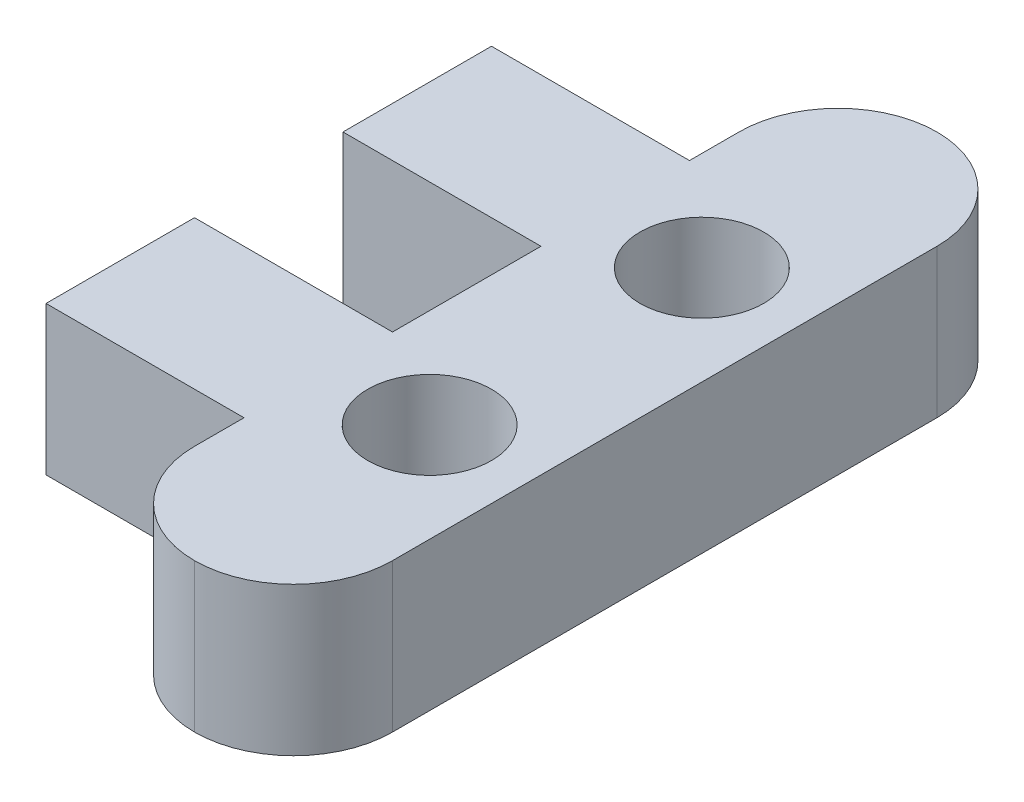
SolidWorks part; units mm, degrees
ref_plane "Front" through (0, 0, 0) normal (0, 0, 1) x (1, 0, 0)
ref_plane "Top" through (0, 0, 0) normal (0, 1, 0) x (1, 0, 0)
ref_plane "Right" through (0, 0, 0) normal (1, 0, 0) x (0, 0, -1)
sketch "Sketch1" plane through (0, 0, 0) normal (0, 1, 0) x (1, 0, 0)
  line L0 (-4, 15) -> (-4, 9)
  line L1 (-4, 15) -> (4, 15)
  line L2 (-12, 9) -> (-12, 3)
  line L3 (-4, -15) -> (4, -15)
  line L7 (-4, 9) -> (-12, 9)
  line L8 (-12, -3) -> (-4, -3)
  line L9 (-4, -9) -> (-4, -15)
  line L10 (-4, -9) -> (-12, -9)
  line L11 (-4, -3) -> (-4, 3)
  line L12 (-4, 3) -> (-12, 3)
  line L13 (-12, -3) -> (-12, -9)
  line L14 (0, -33.7396) -> (0, 36.986) construction
  line L19 (4, 15) -> (4, -15)
  line L21 (4, 0) -> (-4, 0) construction
  circle A0 centre (0, 5.5) radius 2.5
  circle A1 centre (0, -5.5) radius 2.5
  point P0 (0, 0)
  point P19 (0, 15)
  dimension "D4" = 5
  dimension "D2" = 6
  dimension "D3" = 8
  dimension "D1" = 8
  dimension "D5" = 30
  dimension "D6" = 5.5
  dimension "D7" = 5.5
  dimension "D8" = 6
  dimension "D9" = 6
extrude "Boss-Extrude1" add sketch "Sketch1" along normal blind 6
fillet "Fillet1" radius 4 4 edges at (-4, 3, 15) (-4, 3, -15) (4, 3, 15) (4, 3, -15)
equation "\"D7@Sketch1\"=\"D6@Sketch1\""
equation "\"D9@Sketch1\"=(\"D5@Sketch1\"-(3*\"D8@Sketch1\"))/2"
